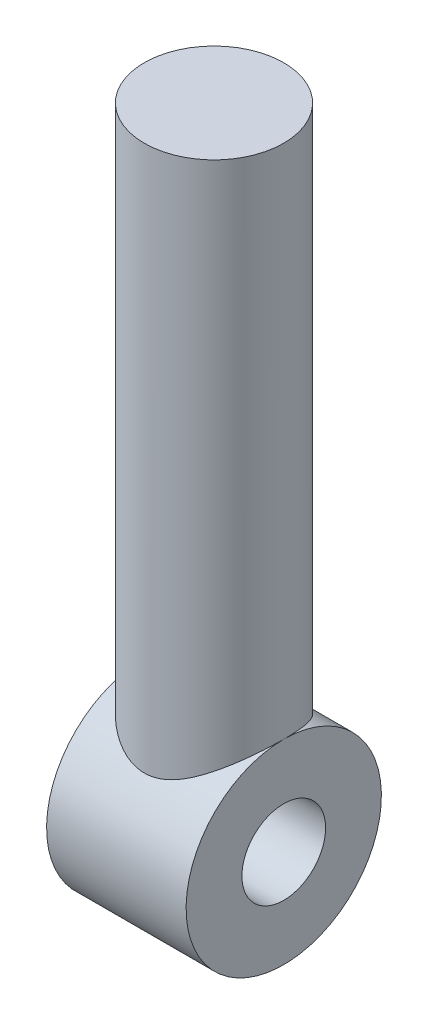
SolidWorks part; units mm, degrees
ref_plane "Front Plane" through (0, 0, 0) normal (0, 0, 1) x (1, 0, 0)
ref_plane "Top Plane" through (0, 0, 0) normal (0, 1, 0) x (1, 0, 0)
ref_plane "Right Plane" through (0, 0, 0) normal (1, 0, 0) x (0, 0, -1)
sketch "Sketch1" plane through (0, 0, 0) normal (0, 1, 0) x (1, 0, 0)
  circle A0 centre (0, 0) radius 1.25
  dimension "D1" = 2.5
extrude "Boss-Extrude1" add sketch "Sketch1" along normal blind 11
sketch "Sketch2" plane through (0, 0, 0) normal (1, 0, 0) x (0, 0, -1)
  circle A0 centre (0, 0) radius 1.75
  dimension "D1" = 3.5
extrude "Boss-Extrude2" add sketch "Sketch2" along normal blind 1.25 and the other way blind 1.25
sketch "Sketch3" plane through (1.25, 0, 0) normal (1, 0, 0) x (0, 0, -1)
  circle A0 centre (0, 0) radius 0.75
  dimension "D1" = 1.5
extrude "Cut-Extrude2" cut sketch "Sketch3" against normal blind 3
